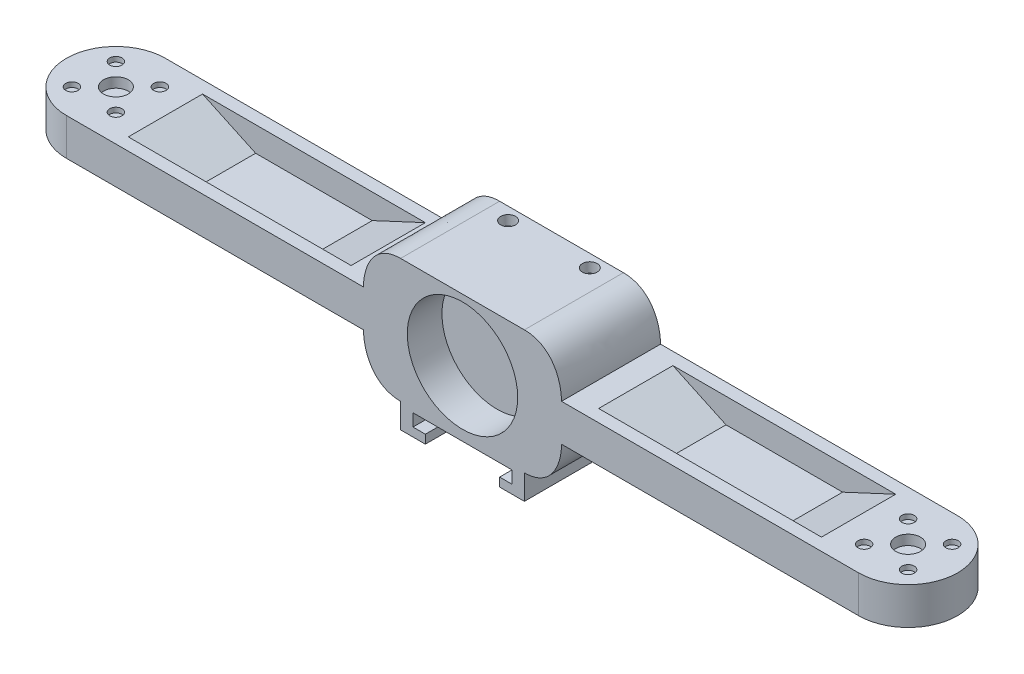
SolidWorks part; units mm, degrees
ref_plane "Front Plane" through (0, 0, 0) normal (0, 0, 1) x (1, 0, 0)
ref_plane "Top Plane" through (0, 0, 0) normal (0, 1, 0) x (1, 0, 0)
ref_plane "Right Plane" through (0, 0, 0) normal (1, 0, 0) x (0, 0, -1)
sketch "Sketch1" plane through (0, 0, 0) normal (0, 1, 0) x (1, 0, 0)
  line L0 (-80, 0) -> (80, 0) construction
  line L1 (-80, 10) -> (80, 10)
  line L2 (-80, -10) -> (80, -10)
  arc A0 (-80, 10) -> (-80, -10) centre (-80, 0) ccw
  arc A1 (80, -10) -> (80, 10) centre (80, 0) ccw
  point P2 (0, 0)
  dimension "D1" = 160
  dimension "D2" = 20
extrude "Boss-Extrude1" add sketch "Sketch1" along normal blind 25 contours L1 A1 L2 A0
sketch "Sketch2" plane through (0, 0, 10) normal (0, 0, 1) x (1, 0, 0)
  line L0 (0, 0) -> (0, 12.5) construction
  circle A0 centre (0, 12.5) radius 11.15
  dimension "D2" = 22.3
  dimension "D1" = 12.5
extrude "Cut-Extrude1" cut sketch "Sketch2" against normal blind 7 contours A0
sketch "Sketch3" plane through (0, 25, 0) normal (0, 1, 0) x (1, 0, 0)
  line L0 (0, 0) -> (20, 0) construction
  line L1 (0, 0) -> (-20, 0) construction
  line L2 (-20, 10) -> (-20, -10)
  line L3 (-80, 10) -> (80, 10) construction
  line L4 (-80, -10) -> (80, -10) construction
  line L5 (20, 10) -> (20, -10)
  line L6 (20, -10) -> (80, -10)
  line L7 (20, 10) -> (80, 10)
  line L8 (-20, 10) -> (-80, 10)
  line L9 (-20, -10) -> (-80, -10)
  arc A0 (-80, 10) -> (-80, -10) centre (-80, 0) ccw
  arc A1 (80, 10) -> (80, -10) centre (80, 0) cw
  dimension "D2" = 20
  dimension "D1" = 20
extrude "Cut-Extrude2" cut sketch "Sketch3" against normal blind 8.75
sketch "Sketch4" plane through (0, 0, 0) normal (0, -1, 0) x (1, 0, 0)
  line L2 (20, 10) -> (20, -10)
  line L3 (-80, 10) -> (80, 10) construction
  line L4 (20, -10) -> (80, -10)
  line L5 (20, 10) -> (80, 10)
  line L6 (-20, 10) -> (-20, -10)
  line L7 (-20, -10) -> (-80, -10)
  line L8 (-20, 10) -> (-80, 10)
  arc A0 (80, 10) -> (80, -10) centre (80, 0) cw
  arc A1 (-80, 10) -> (-80, -10) centre (-80, 0) ccw
extrude "Cut-Extrude3" cut sketch "Sketch4" against normal blind 8.75
sketch "Sketch5" plane through (0, 0, -10) normal (0, 0, -1) x (-1, 0, 0)
  line L0 (0, 0) -> (0, 12.5) construction
  line L2 (-12.5, 2.25) -> (12.5, 2.25)
  line L3 (-12.5, 2.25) -> (-12.5, 22.75)
  line L4 (-12.5, 22.75) -> (12.5, 22.75)
  line L5 (12.5, 2.25) -> (12.5, 22.75)
  line L6 (-12.5, 2.25) -> (12.5, 22.75) construction
  line L7 (-12.5, 22.75) -> (12.5, 2.25) construction
  dimension "D1" = 12.5
  dimension "D2" = 25
  dimension "D3" = 20.5
extrude "Cut-Extrude4" cut sketch "Sketch5" against normal blind 8
sketch "Sketch9" plane through (0, 16.25, 0) normal (0, 1, 0) x (1, 0, 0)
  line L0 (-80, 10) -> (-80, -10) construction
  line L1 (0, 0) -> (0, 5) construction
  circle A0 centre (-80, 0) radius 2.5
  circle A1 centre (80, 0) radius 2.5
  dimension "D1" = 5
  dimension "D2" = 5
extrude "Cut-Extrude5" cut sketch "Sketch9" against normal blind 2
sketch "Sketch10" plane through (0, 16.25, 0) normal (0, 1, 0) x (1, 0, 0)
  line L0 (-80, 0) -> (-80, 4.44) construction
  line L1 (-80, 4.44) -> (-75.56, 4.44) construction
  line L2 (0, 0) -> (0, 5) construction
  circle A0 centre (-75.56, 4.44) radius 1.25
  circle A1 centre (-75.56, -4.44) radius 1.25
  circle A2 centre (-84.44, -4.44) radius 1.25
  circle A3 centre (-84.44, 4.44) radius 1.25
  circle A4 centre (84.44, 4.44) radius 1.25
  circle A5 centre (84.44, -4.44) radius 1.25
  circle A6 centre (75.56, -4.44) radius 1.25
  circle A7 centre (75.56, 4.44) radius 1.25
  point P14 (-80, 0)
  dimension "D3" = 2.5
  dimension "D1" = 4.44
  dimension "D2" = 4.44
  dimension "D5" = 5
  dimension "D4" = 4
extrude "Cut-Extrude6" cut sketch "Sketch10" against normal blind 1
sketch "Sketch13" plane through (0, 8.75, 0) normal (0, -1, 0) x (1, 0, 0)
  line L0 (-80, 10) -> (-80, -10) construction
  line L1 (-80, 0) -> (-75.56, 0) construction
  line L2 (-75.56, 0) -> (-75.56, 4.44) construction
  line L3 (0, 0) -> (0, 5) construction
  circle A0 centre (-75.56, 4.44) radius 2.4
  circle A1 centre (-75.56, -4.44) radius 2.4
  circle A2 centre (-84.44, -4.44) radius 2.4
  circle A3 centre (-84.44, 4.44) radius 2.4
  circle A4 centre (84.44, 4.44) radius 2.4
  circle A5 centre (84.44, -4.44) radius 2.4
  circle A6 centre (75.56, -4.44) radius 2.4
  circle A7 centre (75.56, 4.44) radius 2.4
  point P18 (-80, 0)
  dimension "D1" = 4.44
  dimension "D2" = 4.44
  dimension "D5" = 5
  dimension "D4" = 4
  dimension "D3" = 4.8
extrude "Cut-Extrude7" cut sketch "Sketch13" against normal offset from surface (4.5 mm away) 3 up to face at (84.44, 16.25, -5.69)
sketch "Sketch14" plane through (0, 25, 0) normal (0, 1, 0) x (1, 0, 0)
  line L0 (0, 0) -> (0, 10) construction
  line L1 (-20, 10) -> (20, 10) construction
  line L2 (0, 10) -> (-8.25, 10) construction
  line L3 (-8.25, 10) -> (-8.25, 7.46) construction
  circle A0 centre (-8.25, 7.46) radius 1.5
  circle A1 centre (8.25, 7.46) radius 1.5
  dimension "D3" = 3
  dimension "D1" = 8.25
  dimension "D2" = 2.54
extrude "Cut-Extrude8" cut sketch "Sketch14" against normal blind 2
sketch "Sketch16" plane through (0, 0, -10) normal (0, 0, -1) x (-1, 0, 0)
  line L0 (0, 0) -> (0, 25) construction
  line L1 (20, 25) -> (-20, 25) construction
  line L2 (-12.5, 22.75) -> (-12.5, 25) construction
  line L3 (0, 12.5) -> (-20, 12.5) construction
  line L4 (-12.5, 25) -> (-20, 25)
  line L5 (-20, 25) -> (-20, 16.25)
  line L6 (12.5, 25) -> (20, 25)
  line L7 (20, 25) -> (20, 16.25)
  line L8 (20, 0) -> (20, 8.75)
  line L9 (12.5, 0) -> (20, 0)
  line L10 (-20, 0) -> (-20, 8.75)
  line L11 (-12.5, 0) -> (-20, 0)
  spline S0 degree 3 poles (-20, 16.25) (-20, 20.0915) (-17.8821, 25) (-12.5, 25) knots 0 0 0 0 1 1 1 1
  spline S1 degree 3 poles (20, 16.25) (20, 20.0915) (17.8821, 25) (12.5, 25) knots 0 0 0 0 1 1 1 1
  spline S2 degree 3 poles (20, 8.75) (20, 4.9085) (17.8821, 0) (12.5, 0) knots 0 0 0 0 1 1 1 1
  spline S3 degree 3 poles (-20, 8.75) (-20, 4.9085) (-17.8821, 0) (-12.5, 0) knots 0 0 0 0 1 1 1 1
  dimension "D2" = 20
extrude "Cut-Extrude10" cut sketch "Sketch16" against normal blind 20
sketch "Sketch17" plane through (0, 0, -10) normal (0, 0, -1) x (-1, 0, 0)
  line L0 (12.5, 0) -> (12.5, -5)
  line L1 (-12.5, 0) -> (12.5, 0)
  line L5 (12.5, -5) -> (7.5, -5)
  line L17 (7.5, -5) -> (7.5, -3.25)
  line L18 (7.5, -3.25) -> (10, -3.25)
  line L19 (10, -3.25) -> (10, -0.75)
  line L20 (10, -0.75) -> (-10, -0.75)
  line L21 (-10, -0.75) -> (-10, -3.25)
  line L22 (-10, -3.25) -> (-7.5, -3.25)
  line L23 (-7.5, -3.25) -> (-7.5, -5)
  line L24 (-7.5, -5) -> (-12.5, -5)
  line L25 (-12.5, -5) -> (-12.5, 0)
  dimension "D1" = 20
  dimension "D2" = 25
  dimension "D3" = 2.5
  dimension "D4" = 2.5
  dimension "D5" = 5
  dimension "D6" = 2.5
  dimension "D7" = 1.75
  dimension "D8" = 1.75
  dimension "D9" = 2.5
  dimension "D10" = 5
extrude "Boss-Extrude2" add sketch "Sketch17" against normal blind 20
sketch "Sketch18" plane through (0, 16.25, 0) normal (0, 1, 0) x (1, 0, 0)
  line L0 (0, 0) -> (-20, 0) construction
  line L1 (-20, -10) -> (-20, 10) construction
  line L2 (-90, 0) -> (-70, 0) construction
  line L3 (-20, 0) -> (-25, 0) construction
  line L4 (-70, 0) -> (-25, 0) construction
  line L5 (-20, 10) -> (-25, 10) construction
  line L6 (-20, 10) -> (-80, 10) construction
  line L7 (-25, 10) -> (-25, 7.5) construction
  line L8 (0, 0) -> (0, 10) construction
  line L9 (70, 7.5) -> (25, 7.5)
  line L10 (-70, -7.5) -> (-25, -7.5)
  line L11 (-70, -7.5) -> (-70, 7.5)
  line L12 (-70, 7.5) -> (-25, 7.5)
  line L13 (-25, -7.5) -> (-25, 7.5)
  line L14 (-70, -7.5) -> (-25, 7.5) construction
  line L15 (-70, 7.5) -> (-25, -7.5) construction
  line L16 (25, -7.5) -> (25, 7.5)
  line L17 (70, -7.5) -> (25, -7.5)
  line L18 (70, -7.5) -> (70, 7.5)
  line L19 (70, 7.5) -> (25, -7.5) construction
  line L20 (70, -7.5) -> (25, 7.5) construction
  arc A0 (-80, 10) -> (-80, -10) centre (-80, 0) ccw construction
  point P17 (-47.5, 0)
  point P27 (47.5, 0)
  dimension "D1" = 20
  dimension "D2" = 5
  dimension "D3" = 5
  dimension "D4" = 2.5
  dimension "D5" = 10
extrude "Cut-Extrude11" cut sketch "Sketch18" against normal blind 5
sketch "Sketch20" plane through (0, 0, 10) normal (0, 0, 1) x (1, 0, 0)
  line L0 (-25, 11.25) -> (-25, 16.25)
  line L4 (-25, 11.25) -> (-35.7225, 11.25)
  line L5 (-70, 11.25) -> (-25, 11.25) construction
  line L6 (-35.7225, 11.25) -> (-25, 16.25)
  line L7 (-47.5, 11.25) -> (-47.5, 16.25) construction
  line L8 (-80, 16.25) -> (-20, 16.25) construction
  line L9 (-70, 11.25) -> (-59.2775, 11.25)
  line L10 (-70, 11.25) -> (-70, 16.25)
  line L11 (-59.2775, 11.25) -> (-70, 16.25)
  line L12 (0, 0) -> (0, 25) construction
  line L13 (-12.5, 25) -> (12.5, 25) construction
  line L14 (25, 11.25) -> (35.7225, 11.25)
  line L15 (25, 11.25) -> (25, 16.25)
  line L16 (35.7225, 11.25) -> (25, 16.25)
  line L17 (70, 11.25) -> (70, 16.25)
  line L18 (59.2775, 11.25) -> (70, 16.25)
  line L19 (70, 11.25) -> (59.2775, 11.25)
  dimension "D1" = 65
extrude "Boss-Extrude3" add sketch "Sketch20" against normal blind 20
equation "\"Cent to Cent length\"= 16cm"
equation "\"D1@Sketch1\"=\"Cent to Cent length\""
equation "\"Width\"= 2cm"
equation "\"D2@Sketch1\"=\"Width\""
equation "\"XY for Motor Mounts\"= .444cm"
equation "\"Diam for large MM hole\"= .48cm"
equation "\"Diam for small MM hole\"= .25cm"
equation "\"D1@Sketch10\"=\"XY for Motor Mounts\""
equation "\"D2@Sketch10\"=\"XY for Motor Mounts\""
equation "\"D3@Sketch10\"=\"Diam for small MM hole\""
equation "\"D1@Sketch13\"=\"XY for Motor Mounts\""
equation "\"D2@Sketch13\"=\"XY for Motor Mounts\""
equation "\"D3@Sketch13\"=\"Diam for large MM hole\""
equation "\"Hole distance / 2 for Accelerometer\"= 8.25mm"
equation "\"Hole distance from edge for accelerometer\"= 2.54mm"
equation "\"D1@Sketch14\"=\"Hole distance / 2 for Accelerometer\""
equation "\"D2@Sketch14\"=\"Hole distance from edge for accelerometer\""
equation "\"Center Housing Width/2\"= 2cm"
equation "\"D1@Sketch3\"=\"Center Housing Width/2\""
equation "\"D2@Sketch3\"=\"Center Housing Width/2\""
equation "\"D2@Sketch16\"=\"Center Housing Width/2\""
equation "\"D1@Cut-Extrude10\"=\"Width\""
equation "\"D1@Boss-Extrude2\"=\"Width\""
equation "\"D1@Boss-Extrude3\"=\"Width\""
equation "\"Draft Angle, ESC Recess\"= 65deg"
equation "\"D1@Sketch20\"=\"Draft Angle, ESC Recess\""
equation "\"Screw Depth for Motors\"= .3cm"
equation "\"D1@Cut-Extrude7\"=\"Screw Depth for Motors\""
